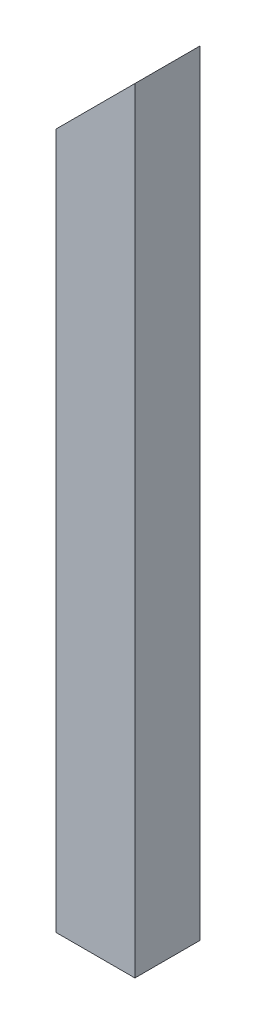
SolidWorks part; units mm, degrees
ref_plane "Front Plane" through (0, 0, 0) normal (0, 0, 1) x (1, 0, 0)
ref_plane "Top Plane" through (0, 0, 0) normal (0, 1, 0) x (1, 0, 0)
ref_plane "Right Plane" through (0, 0, 0) normal (1, 0, 0) x (0, 0, -1)
sketch "Sketch2" plane through (0, 0, 0) normal (0, 0, 1) x (1, 0, 0)
  line L0 (0, -32.5217) -> (0, 47.4783) construction
  line L1 (0, 0) -> (0, 75)
  line L2 (0, 75) -> (8.4853, 83.4853)
  line L3 (0, 75) -> (16.7281, 75) construction
  line L4 (8.4853, 83.4853) -> (8.4853, 0)
  line L5 (8.4853, 0) -> (0, 0)
  dimension "D1" = 75
  dimension "D2" = 12
  dimension "D3" = 45
extrude "Boss-Extrude1" add sketch "Sketch2" along normal mid plane 7
shell "Shell1" thickness 1 removed face at (4.2426, 0, 0) removed face at (4.2426, 79.2426, 0)
